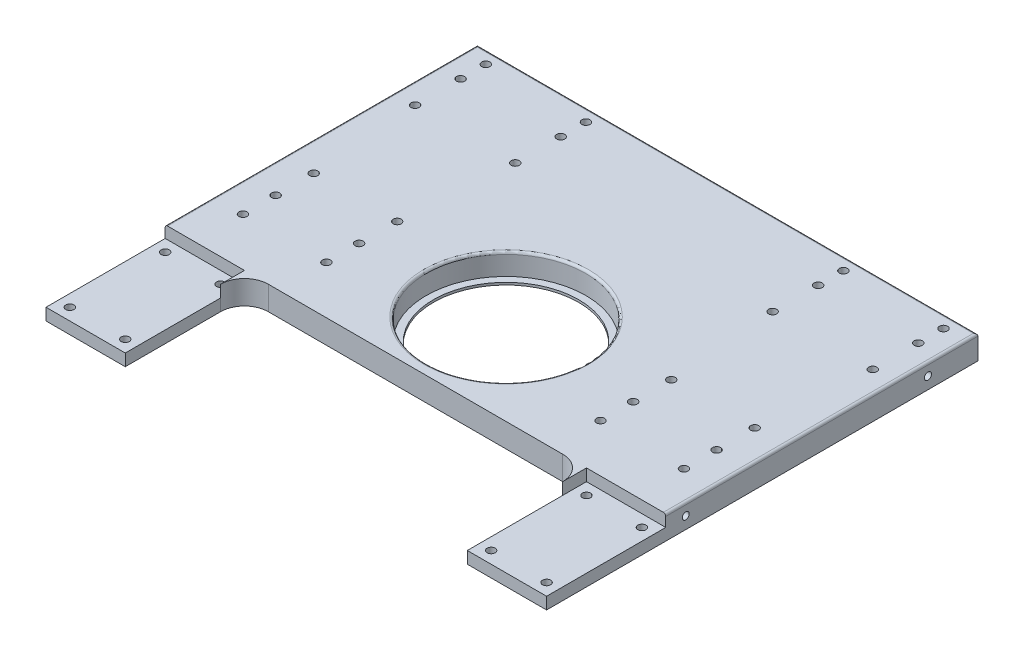
SolidWorks part; units mm, degrees
ref_plane "Ebene vorne" through (0, 0, 0) normal (0, 0, 1) x (1, 0, 0)
ref_plane "Ebene oben" through (0, 0, 0) normal (0, 1, 0) x (1, 0, 0)
ref_plane "Ebene rechts" through (0, 0, 0) normal (1, 0, 0) x (0, 0, -1)
sketch "Skizze1" plane through (0, 0, 0) normal (0, 1, 0) x (1, 0, 0)
  line L1 (-105, -210) -> (105, -210)
  line L2 (-105, -210) -> (-105, 210)
  line L3 (-105, 210) -> (105, 210)
  line L4 (105, -210) -> (105, 210)
  line L5 (-105, -210) -> (105, 210) construction
  line L6 (-105, 210) -> (105, -210) construction
  point P0 (0, 0)
  dimension "D1" = 210
  dimension "D2" = 420
extrude "Aufsatz-Linear austragen1" add sketch "Skizze1" along normal blind 10
ref_plane "Ebene1" through (0, -97.5366, 81.8429) normal (0, -0.766, 0.6428) x (1, 0, 0)
sketch "Skizze2" plane through (0, -97.5366, 81.8429) normal (0, -0.766, 0.6428) x (1, 0, 0)
  line L1 (-105, 167.2972) -> (105, 167.2972) construction
  circle A0 centre (0, 147.2972) radius 5
  dimension "D1" = 10
  dimension "D2" = 20
extrude "Schnitt-Linear austragen1" [suppressed] cut sketch "Skizze2" against normal blind 30 and the other way blind 10
sketch "Skizze3" [suppressed] plane through (0, -67.9923, 57.0523) normal (0, -0.766, 0.6428) x (1, 0, 0)
  circle A0 centre (0, 101.3345) radius 5
  dimension "D1" = 10
extrude "Aufsatz-Linear austragen2" [suppressed] add sketch "Skizze3" along normal blind 0.1
sketch "Skizze4" plane through (0, -97.5366, 81.8429) normal (0, -0.766, 0.6428) x (1, 0, 0)
  line L0 (0, 167.2972) -> (0, 159.9002) construction
  line L1 (-105, 167.2972) -> (105, 167.2972) construction
  line L2 (-25, 167.2972) -> (-25, 202.2972)
  line L3 (-25, 202.2972) -> (25, 202.2972)
  line L4 (-25, 167.2972) -> (25, 167.2972)
  line L5 (25, 167.2972) -> (25, 202.2972)
  point P10 (0, 202.2972)
  dimension "D1" = 50
  dimension "D2" = 35
extrude "Aufsatz-Linear austragen3" [suppressed] add sketch "Skizze4" against normal blind 10 separate body
sketch "Skizze5" plane through (0, 10, 0) normal (0, 1, 0) x (1, 0, 0)
  line L0 (0, 0) -> (0, -210) construction
  line L1 (-105, -210) -> (105, -210) construction
  line L2 (105, -210) -> (18, -210)
  line L3 (-18, -210) -> (-105, -56)
  line L4 (-105, 210) -> (-105, -210) construction
  line L5 (-105, -56) -> (-105, -210)
  line L6 (-105, -210) -> (-18, -210)
  line L7 (105, -56) -> (105, -210)
  line L8 (18, -210) -> (105, -56)
  line L9 (-105, 210) -> (-105, 125)
  line L10 (-105, 125) -> (105, 125)
  line L11 (105, -210) -> (105, 210) construction
  line L12 (105, 125) -> (105, 210)
  line L13 (105, 210) -> (-105, 210)
  line L14 (71.7468, -56) -> (-71.7468, -56)
  line L15 (-71.7468, -56) -> (-2.8247, -178)
  line L16 (71.7468, -56) -> (2.8247, -178)
  line L17 (-2.8247, -178) -> (2.8247, -178)
  line L18 (2.8247, -178) -> (0, -183) construction
  line L19 (-2.8247, -178) -> (0, -183) construction
  point P27 (0, -56)
  dimension "D1" = 36
  dimension "D2" = 154
  dimension "D3" = 85
  dimension "D4" = 32
  dimension "D5" = 27
extrude "Schnitt-Linear austragen2" cut sketch "Skizze5" against normal blind 10
sketch "Skizze6" plane through (0, 10, 0) normal (0, 1, 0) x (1, 0, 0)
  line L0 (0, -210) -> (0, -178) construction
  line L1 (-18, -210) -> (18, -210) construction
  line L2 (-2.8247, -178) -> (2.8247, -178) construction
  line L3 (0, -196.59) -> (-21.075, -196.59) construction
  circle A0 centre (-11, -205) radius 1.7
  circle A1 centre (-11, -188.18) radius 1.7
  circle A2 centre (11, -205) radius 1.7
  circle A3 centre (11, -188.18) radius 1.7
  dimension "D1" = 3.4
  dimension "D2" = 11
  dimension "D3" = 5
  dimension "D4" = 13.41
extrude "Schnitt-Linear austragen3" cut sketch "Skizze6" against normal through all
sketch "Skizze7" plane through (0, 0, 0) normal (0, -1, 0) x (1, 0, 0)
  line L0 (-11, 205) -> (-11, 210) construction
  line L1 (-18, 210) -> (18, 210) construction
  line L2 (-11, 205) -> (-5.1092, 205) construction
  line L3 (-11, 208.4064) -> (-8.05, 206.7032)
  line L4 (-8.05, 206.7032) -> (-8.05, 203.2968)
  line L5 (-11, 201.5936) -> (-8.05, 203.2968)
  line L6 (-11, 201.5936) -> (-13.95, 203.2968)
  line L7 (-13.95, 206.7032) -> (-13.95, 203.2968)
  line L8 (-11, 208.4064) -> (-13.95, 206.7032)
  line L9 (0, 210) -> (0, 121.6034) construction
  line L10 (11, 205) -> (11, 188.18) construction
  line L11 (11, 196.59) -> (0, 196.59) construction
  line L12 (11, 208.4064) -> (8.05, 206.7032)
  line L13 (11, 201.5936) -> (8.05, 203.2968)
  line L14 (8.05, 206.7032) -> (8.05, 203.2968)
  line L15 (11, 201.5936) -> (13.95, 203.2968)
  line L16 (13.95, 206.7032) -> (13.95, 203.2968)
  line L17 (11, 208.4064) -> (13.95, 206.7032)
  line L18 (-8.05, 186.4768) -> (-8.05, 189.8832)
  line L19 (-11, 191.5864) -> (-13.95, 189.8832)
  line L20 (-11, 191.5864) -> (-8.05, 189.8832)
  line L21 (-13.95, 186.4768) -> (-13.95, 189.8832)
  line L22 (-11, 184.7736) -> (-13.95, 186.4768)
  line L23 (-11, 184.7736) -> (-8.05, 186.4768)
  line L24 (8.05, 186.4768) -> (8.05, 189.8832)
  line L25 (11, 191.5864) -> (8.05, 189.8832)
  line L26 (11, 191.5864) -> (13.95, 189.8832)
  line L27 (13.95, 186.4768) -> (13.95, 189.8832)
  line L28 (11, 184.7736) -> (13.95, 186.4768)
  line L29 (11, 184.7736) -> (8.05, 186.4768)
  point P10 (-8.05, 205)
  dimension "D1" = 120
  dimension "D2" = 5.9
extrude "Schnitt-Linear austragen4" cut sketch "Skizze7" against normal blind 4
sketch "Skizze8" plane through (0, 10, 0) normal (0, 1, 0) x (1, 0, 0)
  line L0 (105, 115.41) -> (78.872, 115.41) construction
  line L1 (105, -56) -> (105, 125) construction
  line L2 (-105, 125) -> (105, 125) construction
  dimension "D1" = 9.59
ref_plane "Ebene2" through (0, 62.6966, -52.6087) normal (0, 0.766, -0.6428) x (-1, 0, 0)
sketch "Skizze9" plane through (0, 62.6966, -52.6087) normal (0, 0.766, -0.6428) x (-1, 0, 0)
  line L0 (-105, -81.9813) -> (-78.872, -81.9813) construction
  line L1 (-105, 49.3264) -> (-105, -89.3277) construction
  line L2 (0, -45.2589) -> (0, -16.2619) construction
  circle A0 centre (-100, -81.9813) radius 1.7
  circle A1 centre (100, -81.9813) radius 1.7
  circle A2 centre (-30, -81.9813) radius 1.7
  circle A3 centre (30, -81.9813) radius 1.7
  dimension "D1" = 3.4
  dimension "D2" = 5
  dimension "D3" = 30
extrude "Schnitt-Linear austragen5" [suppressed] cut sketch "Skizze9" against normal through all and the other way through all
ref_plane "Ebene3" through (0, 55.0361, -46.1808) normal (0, 0.766, -0.6428) x (-1, 0, 0)
sketch "Skizze10" [suppressed] plane through (0, 55.0361, -46.1808) normal (0, 0.766, -0.6428) x (-1, 0, 0)
  line L0 (-95, -81.9813) -> (-100, -81.9813) construction
  line L1 (-95, -81.9813) -> (-95, -30.0694) construction
  line L2 (-95, -78.7482) -> (-97.8, -80.3647)
  line L3 (-97.8, -80.3647) -> (-97.8, -83.5979)
  line L4 (-95, -85.2145) -> (-97.8, -83.5979)
  line L5 (-95, -85.2145) -> (-92.2, -83.5979)
  line L6 (-92.2, -80.3647) -> (-92.2, -83.5979)
  line L7 (-95, -78.7482) -> (-92.2, -80.3647)
  line L8 (0, 0) -> (0, -45.6283) construction
  line L9 (-30, -81.9813) -> (-95, -81.9813) construction
  line L10 (-62.5, -81.9813) -> (-62.5, -23.1343) construction
  line L11 (-32.8, -80.3647) -> (-32.8, -83.5979)
  line L12 (-30, -85.2145) -> (-32.8, -83.5979)
  line L13 (-30, -85.2145) -> (-27.2, -83.5979)
  line L14 (-27.2, -80.3647) -> (-27.2, -83.5979)
  line L15 (-30, -78.7482) -> (-27.2, -80.3647)
  line L16 (-30, -78.7482) -> (-32.8, -80.3647)
  line L17 (95, -78.7482) -> (92.2, -80.3647)
  line L18 (92.2, -80.3647) -> (92.2, -83.5979)
  line L19 (95, -85.2145) -> (92.2, -83.5979)
  line L20 (95, -85.2145) -> (97.8, -83.5979)
  line L21 (97.8, -80.3647) -> (97.8, -83.5979)
  line L22 (95, -78.7482) -> (97.8, -80.3647)
  line L23 (30, -78.7482) -> (32.8, -80.3647)
  line L24 (30, -78.7482) -> (27.2, -80.3647)
  line L25 (27.2, -80.3647) -> (27.2, -83.5979)
  line L26 (30, -85.2145) -> (27.2, -83.5979)
  line L27 (30, -85.2145) -> (32.8, -83.5979)
  line L28 (32.8, -80.3647) -> (32.8, -83.5979)
  point P9 (-97.8, -81.9813)
  point P31 (97.8, -81.9813)
  dimension "D1" = 120
  dimension "D2" = 5.6
extrude "Schnitt-Linear austragen6" [suppressed] cut sketch "Skizze10" against normal blind 10 and the other way blind 5
sketch "Skizze13" plane through (0, 10, 0) normal (0, 1, 0) x (1, 0, 0)
  line L0 (71.7468, -56) -> (105, -56) construction
  line L1 (71.7468, -56) -> (96.9548, -70.2409) construction
  line L2 (105, -56) -> (18, -210) construction
  line L3 (0, 0) -> (0, -38.1435) construction
  line L4 (2.8247, -178) -> (71.7468, -56) construction
  line L5 (84.3508, -63.1205) -> (108.762, -19.9098) construction
  line L6 (105, -56) -> (105, 125) construction
  line L7 (88.3734, -56) -> (88.3734, -1) construction
  line L8 (99, -58.9512) -> (105.7595, -46.9862) construction
  line L9 (87.7845, -86.4734) -> (62.5765, -72.2325) construction
  line L10 (77.1638, -80.4734) -> (91.1741, -80.4734) construction
  circle A0 centre (99, -58.9512) radius 1.7
  circle A1 centre (76.9708, -58.9512) radius 1.7
  circle A2 centre (86.8414, -80.4734) radius 1.7
  circle A3 centre (-86.8414, -80.4734) radius 1.7
  circle A4 centre (-99, -58.9512) radius 1.7
  circle A5 centre (-76.9708, -58.9512) radius 1.7
  dimension "D1" = 6
  dimension "D5" = 35
  dimension "D3" = 3.4
  dimension "D6" = 3.4
  dimension "D2" = 6
  dimension "D4" = 6
extrude "Schnitt-Linear austragen7" [suppressed] cut sketch "Skizze13" against normal through all
sketch "Skizze14" plane through (103.579, 0, 58.5154) normal (0.8707, 0, 0.4919) x (0.4919, 0, -0.8707)
  line L0 (-32.111, 5) -> (-32.111, 10)
  line L5 (2.889, 0) -> (2.889, 10) construction
  line L6 (-32.111, 5) -> (2.889, 5)
  line L7 (2.889, 10) -> (-173.9866, 10) construction
  line L8 (-32.111, 10) -> (2.889, 10)
  line L9 (2.889, 10) -> (2.889, 5)
  dimension "D1" = 35
extrude "Schnitt-Linear austragen8" [suppressed] cut sketch "Skizze14" against normal up to surface (28.9525 mm away)
mirror "Spiegeln1" [suppressed] about plane through (0, 0, 0) normal (1, 0, 0)
sketch "Skizze15" [suppressed] plane through (95, 0, 0) normal (1, 0, 0) x (0, 0, -1)
  line L0 (4, 10) -> (4, 0)
  line L1 (4, 0) -> (65, 0)
  line L2 (65, 0) -> (65, 10)
  line L3 (65, 10) -> (4, 10)
extrude "Schnitt-Linear austragen9" [suppressed] cut sketch "Skizze15" against normal through all
sketch "Skizze16" plane through (0, 0, 0) normal (0, -1, 0) x (1, 0, 0)
  line L0 (0, 210) -> (0, 178) construction
  line L1 (-18, 210) -> (18, 210) construction
  line L2 (-2.8247, 178) -> (2.8247, 178) construction
  line L3 (11, 196.59) -> (0, 196.59) construction
  line L4 (11, 205) -> (11, 188.18) construction
  line L6 (-17.5, 193.09) -> (17.5, 193.09)
  line L7 (-17.5, 193.09) -> (-17.5, 200.09)
  line L8 (-17.5, 200.09) -> (17.5, 200.09)
  line L9 (17.5, 193.09) -> (17.5, 200.09)
  line L10 (-17.5, 193.09) -> (17.5, 200.09) construction
  line L11 (-17.5, 200.09) -> (17.5, 193.09) construction
  dimension "D1" = 7
  dimension "D2" = 35
extrude "Schnitt-Linear austragen10" cut sketch "Skizze16" against normal blind 5
sketch "Skizze17" plane through (17.5, 0, 0) normal (-1, 0, 0) x (0, 0, 1)
  line L0 (196.59, 0) -> (196.59, 11.1261) construction
  line L1 (193.09, 0) -> (200.09, 0) construction
  line L2 (193.09, 5) -> (196.59, 8.5)
  line L3 (196.59, 8.5) -> (200.09, 5)
  line L4 (200.09, 5) -> (193.09, 5)
  dimension "D1" = 90
extrude "Schnitt-Linear austragen11" cut sketch "Skizze17" along normal up to surface (35 mm away) up to face at (-17.5, 2.5, 196.59)
sketch "Skizze18" [suppressed] plane through (0, 10, 0) normal (0, 1, 0) x (1, 0, 0)
  line L0 (0, -210) -> (0, 0) construction
  line L1 (-18, -210) -> (18, -210) construction
  line L2 (62.5765, -72.2325) -> (35.4483, -67.5372)
  line L3 (15.3378, -155.8503) -> (-22.1774, -134.6566)
  line L4 (2.8247, -178) -> (62.5765, -72.2325) construction
  line L5 (-15.3378, -155.8503) -> (22.1774, -134.6566)
  line L6 (58.6594, -79.166) -> (40.7308, -76.063)
  line L7 (0, -147.1854) -> (19.5429, -147.1854) construction
  line L8 (0, -95.4) -> (31.4297, -95.4) construction
  line L9 (11.6488, -162.3803) -> (0, -155.7995)
  line L10 (-71.7468, -56) -> (-2.8247, -178) construction
  line L11 (0, -95.4) -> (-37.5153, -116.5937) construction
  line L12 (-37.5153, -116.5937) -> (-39.2566, -117.5774) construction
  line L13 (-11.6488, -162.3803) -> (0, -155.7995)
  line L14 (-58.6594, -79.166) -> (-40.7308, -76.063)
  line L15 (-62.5765, -72.2325) -> (-35.4483, -67.5372)
  circle A0 centre (0, -95.4) radius 33.5
  arc A1 (7.4594, -151.3994) -> (7.4594, -142.9713) centre (9.84, -147.1854) cw
  arc A2 (-7.4594, -151.3994) -> (-7.4594, -142.9713) centre (-9.84, -147.1854) ccw
  circle A3 centre (0, -95.4) radius 45.0879
  point P17 (0, -147.1854)
  point P36 (5, -147.1854)
  point P40 (-5, -147.1854)
  line M16 (62.5765, -72.2325) -> (2.8247, -178)
  line M18 (-2.8247, -178) -> (-71.7468, -56)
  dimension "D2" = 67
  dimension "D5" = 2
  dimension "D4" = 10
  dimension "D1" = 114.6
  dimension "D3" = 7.5
  dimension "D6" = 7.5
extrude "Aufsatz-Linear austragen4" [suppressed] add sketch "Skizze18" against normal blind 10 contours A3 L15 L14 M18 | A3 A0 M16 M18 | A3 L6 L2 M16 | A2 L5 L3 | A3 L3 L5 | L3 A1 L5 | L13 L9 L3 L5 M18 M16
sketch "Skizze19" [suppressed] plane through (0, 0, 0) normal (0, -1, 0) x (1, 0, 0)
  circle A0 centre (0, 35.4) radius 31.5
  circle A1 centre (0, 35.4) radius 33.5
  circle A2 centre (0, 35.4) radius 33.5 construction
  dimension "D1" = 63
extrude "Aufsatz-Linear austragen5" [suppressed] add sketch "Skizze19" against normal blind 1
sketch "Skizze20" plane through (0, 10, 0) normal (0, 1, 0) x (1, 0, 0)
  line L0 (105, 119.52) -> (55.4083, 119.52) construction
  line L1 (105, -56) -> (105, 125) construction
  line L2 (-105, 125) -> (105, 125) construction
  line L3 (0, 125) -> (0, 96.9732) construction
  line L4 (92.5, 43.82) -> (57.5, 43.82) construction
  line L5 (96, 119.52) -> (96, 16.5236) construction
  line L6 (92.5, 43.82) -> (92.5, -19.0314) construction
  line L7 (75, 43.82) -> (75, 8.7303) construction
  circle A0 centre (96, 119.52) radius 1.7
  circle A1 centre (54, 119.52) radius 1.7
  circle A2 centre (-54, 119.52) radius 1.7
  circle A3 centre (-96, 119.52) radius 1.7
  circle A4 centre (92.5, 43.82) radius 1.7
  circle A5 centre (57.5, 43.82) radius 1.7
  circle A6 centre (-92.5, 43.82) radius 1.7
  circle A7 centre (-57.5, 43.82) radius 1.7
  circle A8 centre (96, 108.94) radius 1.7
  circle A9 centre (92.5, 27.84) radius 1.7
  circle A10 centre (54, 108.94) radius 1.7
  circle A11 centre (57.5, 27.84) radius 1.7
  circle A12 centre (-54, 108.94) radius 1.7
  circle A13 centre (-96, 108.94) radius 1.7
  circle A14 centre (-57.5, 27.84) radius 1.7
  circle A15 centre (-92.5, 27.84) radius 1.7
  circle A16 centre (96, 89.84) radius 1.7
  circle A17 centre (92.5, 14.13) radius 1.7
  circle A18 centre (57.5, 14.13) radius 1.7
  circle A19 centre (54, 89.84) radius 1.7
  circle A20 centre (-96, 89.84) radius 1.7
  circle A21 centre (-54, 89.84) radius 1.7
  circle A22 centre (-57.5, 14.13) radius 1.7
  circle A23 centre (-92.5, 14.13) radius 1.7
  dimension "D1" = 3.4
  dimension "D2" = 5.48
  dimension "D3" = 9
  dimension "D4" = 42
  dimension "D5" = 75.7
  dimension "D6" = 12.5
  dimension "D7" = 35
  dimension "D8" = 10.58
  dimension "D9" = 15.98
  dimension "D10" = 19.1
  dimension "D11" = 13.71
extrude "Schnitt-Linear austragen12" cut sketch "Skizze20" against normal through all
sketch "Skizze21" plane through (0, 10, 0) normal (0, 1, 0) x (1, 0, 0)
  line L0 (-71.7468, -56) -> (-71.7468, -6)
  line L1 (-71.7468, -6) -> (71.7468, -6)
  line L2 (71.7468, -6) -> (71.7468, -56)
  line L3 (71.7468, -56) -> (-71.7468, -56) construction
  line L4 (-71.7468, -56) -> (71.7468, -56)
  dimension "D1" = 50
extrude "Schnitt-Linear austragen13" cut sketch "Skizze21" against normal through all
sketch "Skizze22" plane through (0, 10, 0) normal (0, 1, 0) x (1, 0, 0)
  line L0 (-71.7468, -56) -> (-2.8247, -178)
  arc A0 (-71.7468, -56) -> (-2.8247, -178) centre (55.7113, -64.4627) ccw
  line M19 (-2.8247, -178) -> (-71.7468, -56)
extrude "Schnitt-Linear austragen14" cut sketch "Skizze22" against normal through all contours M19 region at (-44.6278, 10, 121.1478)
sketch "Skizze23" plane through (0, 10, 0) normal (0, 1, 0) x (1, 0, 0)
  line L0 (-18, -210) -> (-105, -56) construction
  line L1 (-105, -56) -> (-18, -210)
  arc A0 (-18, -210) -> (-105, -56) centre (108.9155, -36.7263) cw
  arc A2 (-71.7468, -56) -> (-2.8247, -178) centre (55.7113, -64.4627) ccw construction
  dimension "D1" = 60
extrude "Aufsatz-Linear austragen6" add sketch "Skizze23" against normal blind 10
mirror "Spiegeln2" about plane through (0, 0, 0) normal (1, 0, 0) of "Aufsatz-Linear austragen6", "Schnitt-Linear austragen14"
sketch "Skizze25" plane through (0, 10, 0) normal (0, 1, 0) x (1, 0, 0)
  line L0 (-105, -56) -> (-71.7468, -56) construction
  line L1 (-105, -6) -> (-105, -56) construction
  line L2 (-105, -6) -> (-71.7468, -6) construction
  line L3 (-71.7468, -6) -> (-71.7468, -56) construction
  line L4 (-88.3734, -6) -> (-88.3734, -56) construction
  line L5 (-105, -31) -> (-71.7468, -31) construction
  line L6 (-105, 125) -> (-105, -56) construction
  circle A0 centre (-100, -11) radius 1.7
  circle A1 centre (-76.7468, -11) radius 1.7
  circle A2 centre (-76.7468, -51) radius 1.7
  circle A3 centre (-100, -51) radius 1.7
  dimension "D2" = 3.4
  dimension "D1" = 50
  dimension "D3" = 5
  dimension "D4" = 5
extrude "Schnitt-Linear austragen15" cut sketch "Skizze25" against normal through all
sketch "Skizze26" plane through (-105, 0, 0) normal (-1, 0, 0) x (0, 0, 1)
  line L0 (6, 5) -> (6, 13.1015)
  line L1 (56, 0) -> (56, 10) construction
  line L2 (56, 5) -> (6, 5)
  line L4 (-125, 0) -> (56, 0) construction
  line L5 (56, 5) -> (56, 0)
  line L6 (6, 13.1015) -> (200.6846, 82.5463)
  line L7 (200.6846, 82.5463) -> (242.9972, -41.0376)
  line L8 (242.9972, -41.0376) -> (91.2415, -60.2848)
  line L9 (91.2415, -60.2848) -> (56, 0)
  dimension "D1" = 50
mirror "Spiegeln3" about plane through (0, 0, 0) normal (1, 0, 0) of "Schnitt-Linear austragen15"
extrude "Schnitt-Linear austragen16" cut sketch "Skizze26" against normal through all
sketch "Skizze27" plane through (0, 10, 0) normal (0, 1, 0) x (1, 0, 0)
  line L0 (0, -6) -> (0, 125) construction
  line L1 (105, -6) -> (-105, -6) construction
  line L2 (-105, 125) -> (105, 125) construction
  line L3 (105, -6) -> (-105, -6) construction
  circle A0 centre (0, 32) radius 33.5
  dimension "D1" = 67
  dimension "D2" = 38
extrude "Schnitt-Linear austragen17" cut sketch "Skizze27" against normal through all
sketch "Skizze28" plane through (0, 0, 0) normal (0, -1, 0) x (1, 0, 0)
  circle A0 centre (0, -32) radius 30.5
  circle A1 centre (0, -32) radius 33.5 construction
  circle A2 centre (0, -32) radius 36.0063
  dimension "D1" = 3
extrude "Aufsatz-Linear austragen7" add sketch "Skizze28" against normal blind 1
sketch "Skizze29" plane through (-105, 0, 0) normal (-1, 0, 0) x (0, 0, 1)
  line L0 (-125, 5) -> (-93.4233, 5) construction
  line L1 (-125, 0) -> (-125, 10) construction
  circle A0 centre (-104, 5) radius 1.5
  circle A1 centre (-2.4, 5) radius 1.45
  dimension "D1" = 3
  dimension "D3" = 2.9
  dimension "D2" = 21
extrude "Schnitt-Linear austragen18" cut sketch "Skizze29" against normal blind 10
sketch "Skizze30" plane through (0, 0, -125) normal (0, 0, -1) x (-1, 0, 0)
  line L0 (105, 5) -> (60.2539, 5) construction
  line L1 (105, 0) -> (105, 10) construction
  line L2 (0, 0) -> (0, 19.3538) construction
  line L3 (105, 0) -> (-105, 0) construction
  circle A0 centre (100, 5) radius 1.45
  circle A1 centre (84, 5) radius 1.45
  dimension "D1" = 2.9
  dimension "D2" = 5
  dimension "D3" = 21
extrude "Schnitt-Linear austragen19" cut sketch "Skizze30" against normal blind 10
mirror "Spiegeln4" about plane through (0, 0, 0) normal (1, 0, 0) of "Schnitt-Linear austragen18", "Schnitt-Linear austragen19"
sketch "Skizze31" plane through (0, 0, 0) normal (0, -1, 0) x (1, 0, 0)
  line L0 (0, -125) -> (0, -73.0202) construction
  line L1 (-105, -125) -> (105, -125) construction
  circle A0 centre (-96, -119.52) radius 2.95
  circle A1 centre (-54, -119.52) radius 2.95
  circle A2 centre (-92.5, -43.82) radius 2.95
  circle A3 centre (-57.5, -43.82) radius 2.95
  circle A4 centre (57.5, -43.82) radius 2.95
  circle A5 centre (92.5, -43.82) radius 2.95
  circle A6 centre (54, -119.52) radius 2.95
  circle A7 centre (96, -119.52) radius 2.95
  circle A8 centre (-96, -108.94) radius 2.95
  circle A9 centre (-96, -89.84) radius 2.95
  circle A10 centre (-54, -89.84) radius 2.95
  circle A11 centre (-54, -108.94) radius 2.95
  circle A12 centre (-92.5, -14.13) radius 2.95
  circle A13 centre (-92.5, -27.84) radius 2.95
  circle A14 centre (-57.5, -27.84) radius 2.95
  circle A15 centre (-57.5, -14.13) radius 2.95
  circle A16 centre (54, -108.94) radius 2.95
  circle A17 centre (54, -89.84) radius 2.95
  circle A18 centre (96, -89.84) radius 2.95
  circle A19 centre (96, -108.94) radius 2.95
  circle A20 centre (57.5, -14.13) radius 2.95
  circle A21 centre (57.5, -27.84) radius 2.95
  circle A22 centre (92.5, -27.84) radius 2.95
  circle A23 centre (92.5, -14.13) radius 2.95
  dimension "D1" = 5.9
extrude "Schnitt-Linear austragen20" cut sketch "Skizze31" against normal blind 3.5
move or copy body "Körper-Verschieben/Kopieren1" [suppressed] bodies to move or copy 132 copy no rotation origin (0, 5, -34.5) rotation axis (1, 0, 0) rotation angle 90
sketch "Skizze32" plane through (0, 10, 0) normal (0, 1, 0) x (1, 0, 0)
  line L1 (25.1613, 106.641) -> (-1.8387, 106.641)
  line L2 (25.1613, 106.641) -> (25.1613, 77.141)
  line L3 (25.1613, 77.141) -> (-1.8387, 77.141)
  line L4 (-1.8387, 106.641) -> (-1.8387, 77.141)
  line L5 (25.1613, 106.641) -> (-1.8387, 77.141) construction
  line L6 (25.1613, 77.141) -> (-1.8387, 106.641) construction
  circle A0 centre (25.1613, 77.141) radius 1.45
  circle A1 centre (-1.8387, 77.141) radius 1.45
  circle A2 centre (-1.8387, 106.641) radius 1.45
  circle A3 centre (25.1613, 106.641) radius 1.45
  point P0 (11.6613, 91.891)
  dimension "D3" = 2.9
  dimension "D1" = 29.5
  dimension "D2" = 27
extrude "Schnitt-Linear austragen21" [suppressed] cut sketch "Skizze32" against normal through all contours L3 A0 L2 | L2 A0 L3 | L4 A1 L3 | L3 A1 L4 | L1 A2 L4 | L4 A2 L1 | L2 A3 L1 | L1 A3 L2
fillet "Verrundung1" radius 10 2 edges at (-71.7468, 2.5, 6) (71.7468, 2.5, 6)
sketch "Skizze33" plane through (0, 5, 0) normal (0, 1, 0) x (1, 0, 0)
  line L0 (-71.7468, -16) -> (-71.7468, -6)
  line L1 (-61.7468, -6) -> (-105, -6) construction
  line L2 (-71.7468, -6) -> (-61.7468, -6)
  line L3 (105, -6) -> (-105, -6) construction
  line L4 (0, -6) -> (0, -39.688) construction
  line L5 (71.7468, -6) -> (61.7468, -6)
  line L6 (71.7468, -16) -> (71.7468, -6)
  arc A0 (-61.7468, -6) -> (-71.7468, -16) centre (-61.7468, -16) ccw construction
  arc A1 (-71.7468, -16) -> (-61.7468, -6) centre (-61.7468, -16) cw
  arc A2 (71.7468, -16) -> (61.7468, -6) centre (61.7468, -16) ccw
extrude "Aufsatz-Linear austragen8" add sketch "Skizze33" along normal up to surface (5 mm away) up to face at (0, 10, 1.5)
fillet "Verrundung2" radius 1 4 edges at (0, 10, 1.5) (105, 10, -59.5) (0, 10, -125) (-105, 10, -59.5)
sketch "Skizze34" plane through (0, 10, 0) normal (0, 1, 0) x (1, 0, 0)
  line L0 (54, 121.22) -> (-54, 121.22) construction
  circle A0 centre (-54, 119.52) radius 1.7 construction
  circle A1 centre (54, 119.52) radius 1.7 construction
  text T0 "OpenAstroTech" font "@Adobe Heiti Std R" height in points 22
extrude "Schnitt-Linear austragen22" [suppressed] cut sketch "Skizze34" against normal blind 0.8
sketch "Skizze35" plane through (0, 10, 0) normal (0, 1, 0) x (1, 0, 0)
  line L0 (0, 124) -> (0, 69.8916) construction
  line L1 (104, 124) -> (-104, 124) construction
  circle A0 centre (26.9, 117.4942) radius 1.45
  circle A1 centre (26.9, 86.4942) radius 1.45
  circle A2 centre (-26.9, 86.4942) radius 1.45
  circle A3 centre (-26.9, 117.4942) radius 1.45
  dimension "D1" = 2.9
  dimension "D2" = 53.8
  dimension "D3" = 31
extrude "Schnitt-Linear austragen23" [suppressed] cut sketch "Skizze35" against normal blind 10
chamfer "Fase1" distance 0.62 angle 45 47 edges at (-96, 3.5, -91.54) (-96, 3.5, -92.79) (-96, 3.5, -110.64) (-96, 3.5, -111.89) (-96, 3.5, -121.22) (-96, 3.5, -122.47) (-92.5, 3.5, -45.52) (-92.5, 3.5, -46.77) (-92.5, 3.5, -29.54) (-92.5, 3.5, -30.79) (-92.5, 3.5, -15.83) (-92.5, 3.5, -17.08) (-57.5, 3.5, -15.83) (-57.5, 3.5, -17.08) (-57.5, 3.5, -29.54) (-57.5, 3.5, -30.79) (-57.5, 3.5, -45.52) (-57.5, 3.5, -46.77) (-54, 3.5, -91.54) (-54, 3.5, -92.79) (-54, 3.5, -110.64) (-54, 3.5, -111.89) (57.5, 3.5, -12.43) (57.5, 3.5, -11.18) (57.5, 3.5, -26.14) (57.5, 3.5, -24.89) (57.5, 3.5, -42.12) (57.5, 3.5, -40.87) (54, 3.5, -88.14) (54, 3.5, -86.89) (54, 3.5, -107.24) (54, 3.5, -105.99) (54, 3.5, -117.82) (54, 3.5, -116.57) (96, 3.5, -117.82) (96, 3.5, -116.57) (96, 3.5, -107.24) (96, 3.5, -105.99) (-54, 3.5, -122.47) (96, 3.5, -88.14) (96, 3.5, -86.89) (92.5, 3.5, -42.12) (92.5, 3.5, -40.87) (92.5, 3.5, -26.14) (92.5, 3.5, -24.89) (92.5, 3.5, -12.43) (92.5, 3.5, -11.18)
sketch "Skizze36" plane through (0, 10, 0) normal (0, 1, 0) x (1, 0, 0)
  line L0 (-117.051, 68.7567) -> (-66.9468, 68.7567)
  line L1 (-66.9468, 68.7567) -> (-66.9468, 137.1475)
  line L2 (-66.9468, 137.1475) -> (152.3569, 201.2504)
  line L3 (152.3569, 201.2504) -> (200.3815, -97.7642)
  line L4 (200.3815, -97.7642) -> (-142.4512, -123.0035)
  line L5 (-142.4512, -123.0035) -> (-163.1334, 56.1249)
  line L6 (-163.1334, 56.1249) -> (-117.051, 68.7567)
extrude "Schnitt-Linear austragen24" [suppressed] cut sketch "Skizze36" against normal through all
